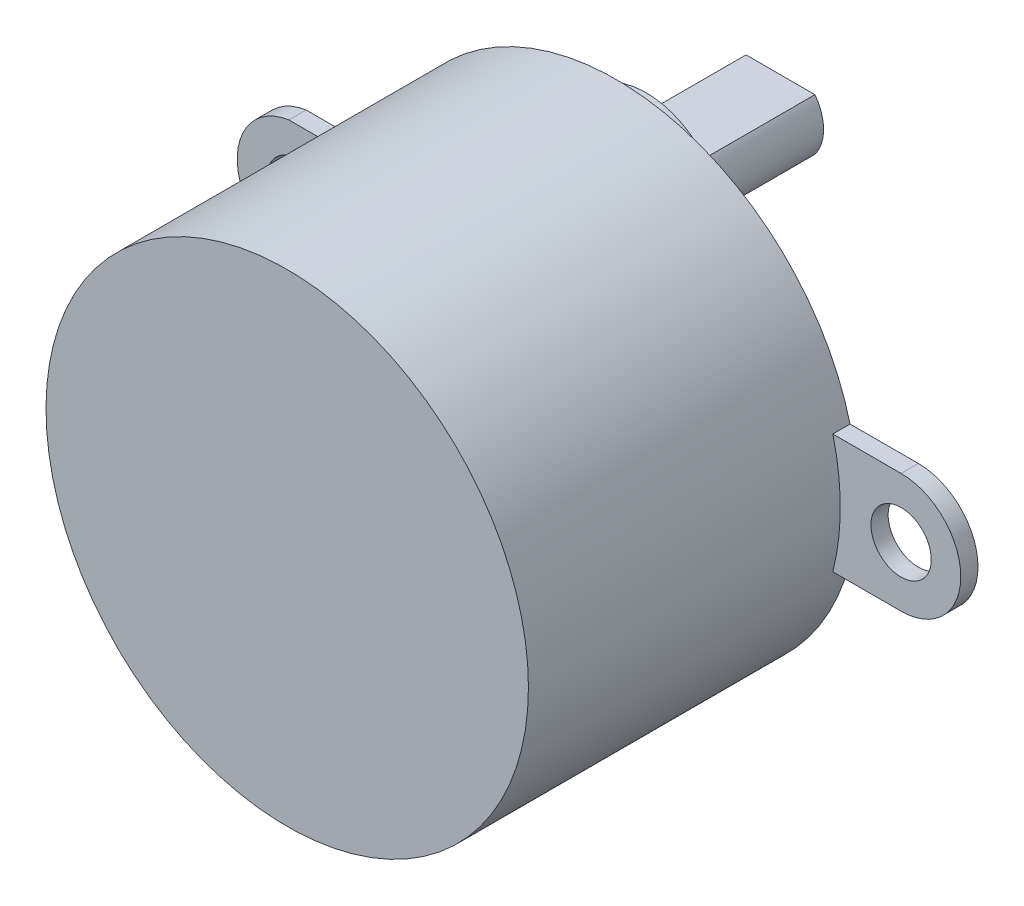
SolidWorks part; units mm, degrees
ref_plane "Front Plane" through (0, 0, 0) normal (0, 0, 1) x (1, 0, 0)
ref_plane "Top Plane" through (0, 0, 0) normal (0, 1, 0) x (1, 0, 0)
ref_plane "Right Plane" through (0, 0, 0) normal (1, 0, 0) x (0, 0, -1)
sketch "Sketch1" plane through (0, 0, 0) normal (0, 0, 1) x (1, 0, 0)
  line L0 (0.0277, 9.5) -> (0.0277, 6.5)
  line L1 (-1.9723, 9.5) -> (2.0277, 9.5)
  line L2 (-1.9723, 6.5) -> (2.0277, 6.5)
  line L3 (0.0277, 16.5362) -> (17.5277, 16.5362)
  line L4 (0.0277, 16.5362) -> (-17.5, 16.5362)
  line L5 (-18.0037, 3.4636) -> (-13.5648, 3.4636)
  line L7 (-18.0037, -3.4636) -> (-13.5648, -3.4636)
  line L9 (17.5277, 3.4636) -> (13.5648, 3.4636)
  line L11 (17.5277, -3.4636) -> (13.5648, -3.4636)
  circle A0 centre (0, 0) radius 14
  circle A1 centre (0.0277, 8) radius 4.5
  circle A2 centre (0.0277, 8) radius 2.5
  arc A3 (2.0277, 9.5) -> (2.0277, 6.5) centre (0.0277, 8) cw
  arc A4 (-1.9723, 9.5) -> (-1.9723, 6.5) centre (0.0277, 8) ccw
  circle A5 centre (-17.5, 0) radius 1.75
  circle A6 centre (17.5277, 0) radius 1.75
  arc A9 (-18.0037, 3.4636) -> (-18.0037, -3.4636) centre (-17.5, 0) ccw
  arc A10 (17.5277, 3.4636) -> (17.5277, -3.4636) centre (17.5277, 0) cw
  point P9 (0.0277, 8)
  point P12 (0.0277, 9.5)
  point P15 (0.0277, 6.5)
  dimension "D1" = 8
extrude "Boss-Extrude1" add sketch "Sketch1" along normal blind 19.1 contours A0
extrude "Boss-Extrude2" add sketch "Sketch1<3>" against normal blind 1.7 contours A1 A2 region at (-4.345, 8, 0)
sketch "Sketch1<3>" plane through (0, 0, 0) normal (0, 0, 1) x (1, 0, 0) same geometry as "Sketch1"
extrude "Boss-Extrude4" add sketch "Sketch1<6>" against normal blind 2.3 contours A2 region at (0.0277, 9.9077, 0)
sketch "Sketch1<6>" plane through (0, 0, 0) normal (0, 0, 1) x (1, 0, 0) same geometry as "Sketch1"
extrude "Boss-Extrude5" add sketch "Sketch1<7>" against normal blind 9.5 contours L2 A2 L1 L0 | L1 A2 L2 L0 region at (1.2026, 8, 0) region at (-1.1472, 8, 0)
sketch "Sketch1<7>" plane through (0, 0, 0) normal (0, 0, 1) x (1, 0, 0) same geometry as "Sketch1"
extrude "Boss-Extrude6" add sketch "Sketch1<8>" against normal blind 2.3 contours L2 A2 region at (0.0277, 6.0922, 0)
sketch "Sketch1<8>" plane through (0, 0, 0) normal (0, 0, 1) x (1, 0, 0) same geometry as "Sketch1"
extrude "Boss-Extrude7" add sketch "Sketch1<9>" along normal blind 1 contours L5 A9 L7 A0 A5 | A10 L9 A0 L11 A6 region at (-15.7843, 3.3619, 0) region at (15.5462, 3.362, 0)
sketch "Sketch1<9>" plane through (0, 0, 0) normal (0, 0, 1) x (1, 0, 0) same geometry as "Sketch1"
